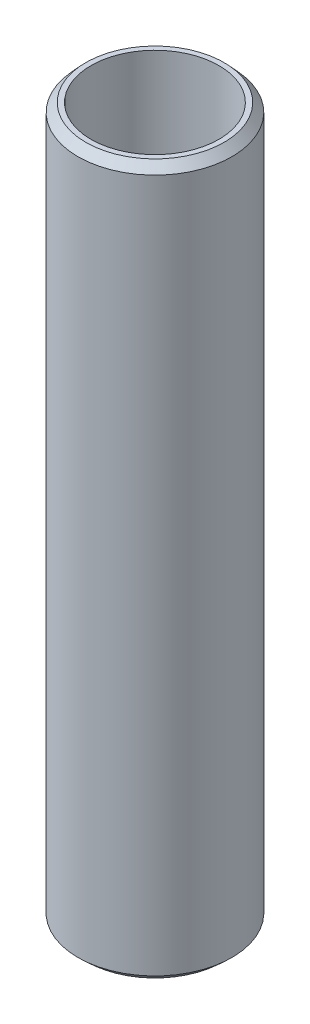
SolidWorks part; units mm, degrees
ref_plane "Front Plane" through (0, 0, 0) normal (0, 0, 1) x (1, 0, 0)
ref_plane "Top Plane" through (0, 0, 0) normal (0, 1, 0) x (1, 0, 0)
ref_plane "Right Plane" through (0, 0, 0) normal (1, 0, 0) x (0, 0, -1)
sketch "Sketch1" plane through (0, 0, 0) normal (0, 1, 0) x (1, 0, 0)
  circle A0 centre (0, 0) radius 35
  dimension "SHAFT_OD" = 70
extrude "Boss-Extrude1" add sketch "Sketch1" along normal blind 322.7709
sketch "Sketch2" plane through (0, 0, 0) normal (0, 1, 0) x (1, 0, 0)
  circle A0 centre (0, 0) radius 29.0846
  dimension "BORE_D" = 58.1693
extrude "Cut-Extrude1" cut sketch "Sketch2" along normal through all
chamfer "Chamfer1" distance 3.8779 angle 42.528 2 edges at (0, 322.7709, 35) (0, 0, 35) first distance on face at (0, 322.7709, 35) first distance on face at (0, 0, 29.0846)
